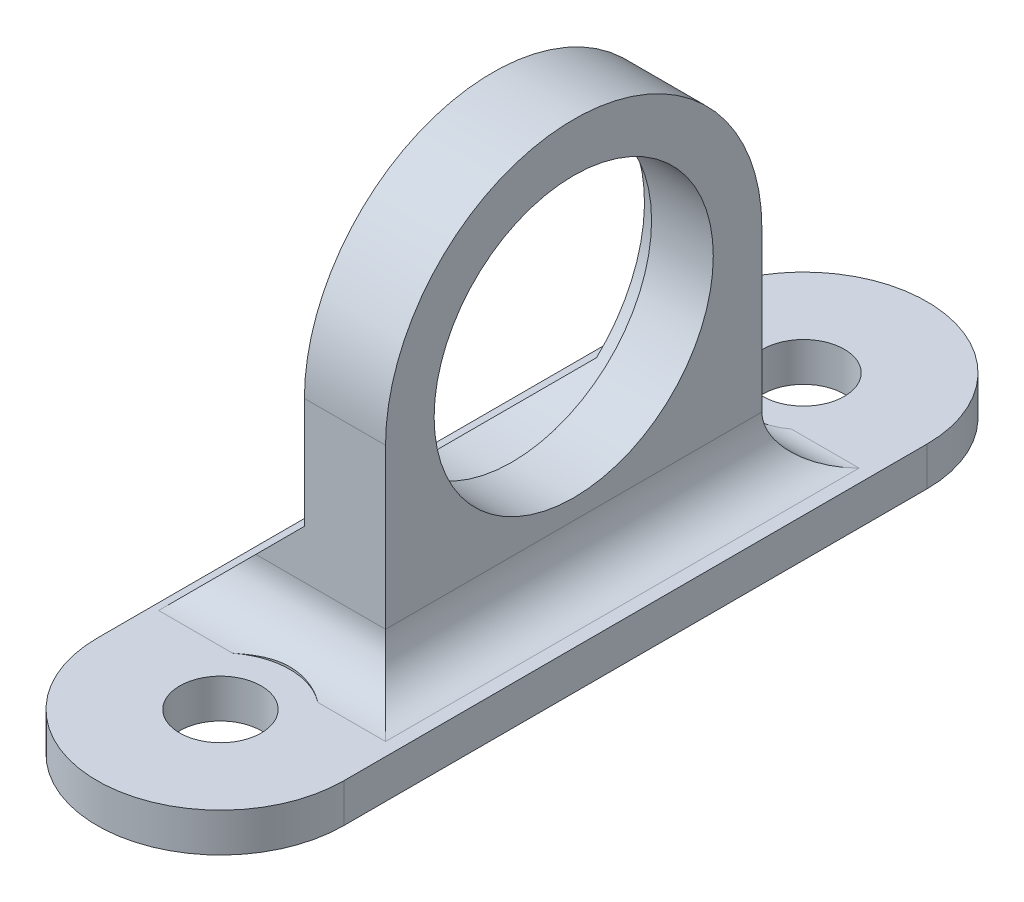
SolidWorks part; units mm, degrees
ref_plane "Front Plane" through (0, 0, 0) normal (0, 0, 1) x (1, 0, 0)
ref_plane "Top Plane" through (0, 0, 0) normal (0, 1, 0) x (1, 0, 0)
ref_plane "Right Plane" through (0, 0, 0) normal (1, 0, 0) x (0, 0, -1)
sketch "Sketch1" plane through (0, 0, 0) normal (1, 0, 0) x (0, 0, -1)
  line L0 (0, 0) -> (18.2171, 0) construction
  line L2 (0, -32.4) -> (60.1006, -32.4) construction
  circle A6 centre (0, -7) radius 14.3637
  circle A10 centre (0, -7) radius 19.3637
  point P6 (0, -7)
  point P15 (0, 0)
  point P17 (0, 0)
  dimension "D1" = 5
  dimension "D5" = 28.7274
  dimension "D4" = 7
  dimension "D9" = 25.4
extrude "Motor face and screw extrude" add sketch "Sketch1" along normal blind 6.35 contours A10 A6 region at (0, -7, 18.816)
ref_axis "Axis1" through (-6.6, 0, 0) along (1, 0, 0)
ref_plane "Extrusion Plne" through (0, -32.4, 0) normal (0, 1, 0) x (1, 0, 0)
sketch "Sketch7" plane through (0, 0, 0) normal (-1, 0, 0) x (0, 0, 1)
  circle A0 centre (0, -7) radius 14.3637 construction
  circle A1 centre (0, -7) radius 14.3637 construction
  circle A2 centre (0, -7) radius 15.6337
  circle A3 centre (0, -7) radius 19.3637 construction
  circle A4 centre (0, -7) radius 19.3637
  circle M4 centre (0, -7) radius 19.3637
  dimension "D1" = 31.2674
extrude "Boss-Extrude4" add sketch "Sketch7" along normal blind 2 contours A2 M4 | A4 | A2 region at (0, -7, -18.816)
sketch "Sketch3" plane through (0, -32.4, 0) normal (0, 1, 0) x (1, 0, 0)
  line L0 (0, 0) -> (0, 60.1006) construction
  line L1 (12.7, 0) -> (-12.7, 0) construction
  line L5 (-12.7, -30) -> (-12.7, 30)
  line L6 (0, 0) -> (0, 60.1006) construction
  line L7 (12.7, -30) -> (12.7, 30)
  arc A0 (-12.7, 30) -> (0, 17.3) centre (0, 30) ccw construction
  circle A1 centre (0, 30) radius 4.2
  arc A2 (12.7, 30) -> (-12.7, 30) centre (0, 30) ccw
  arc A3 (-12.7, -30) -> (0, -17.3) centre (0, -30) cw construction
  arc A4 (12.7, -30) -> (-12.7, -30) centre (0, -30) cw
  circle A5 centre (0, -30) radius 4.2
  point P9 (0, 0)
  dimension "D1" = 25.4
  dimension "D2" = 8.4
  dimension "D3" = 30
extrude "Boss-Extrude3" add sketch "Sketch3" along normal blind 4 separate body
sketch "Sketch8" plane through (0, -28.4, 0) normal (0, 1, 0) x (1, 0, 0)
  line L0 (6.35, 19.3637) -> (-2, 19.3637) construction
  line L1 (6.35, -19.3637) -> (6.35, 19.3637) construction
  line L2 (-2, 19.3637) -> (-2, -19.3637) construction
  line L3 (-2, -19.3637) -> (6.35, -19.3637) construction
  line L4 (6.35, 19.3637) -> (-2, 19.3637)
  line L5 (6.35, -19.3637) -> (6.35, 19.3637)
  line L6 (-2, 19.3637) -> (-2, -19.3637)
  line L7 (-2, -19.3637) -> (6.35, -19.3637)
extrude "Boss-Extrude5" add sketch "Sketch8" along normal up to next
chamfer "Chamfer1" distance 10 angle 45 1 edges at (-2, -28.4, 0)
fillet "Fillet1" radius 5 3 edges at (-2.825, -28.4, 19.3637) (6.35, -28.4, 0) (-2.825, -28.4, -19.3637)
hole_wizard "Ø1.0mm Dowel Hole1" positions "Sketch5" profile "Sketch6" hole size "Ø1.0" standard "ANSI Metric" end condition through all
sketch "Sketch5" plane through (0, -28.4, 0) normal (0, 1, 0) x (1, 0, 0)
  point P0 (0, -30)
  point P3 (0, 30)
sketch "Sketch6" plane through (0, -28.4, 30) normal (1, 0, 0) x (0, 0, -1)
  line L0 (0, 0) -> (0, 40.7637)
  line L1 (0, 40.7637) -> (7.1437, 40.7637)
  line L2 (7.1437, 40.7637) -> (7.1437, 0)
  line L5 (7.1437, 0) -> (0, 0)
  line L11 (0, -6.35) -> (0, 107.95) construction
  dimension "Thru Hole Dia." = 14.2875
  dimension "Thru Hole Depth" = 40.7637
